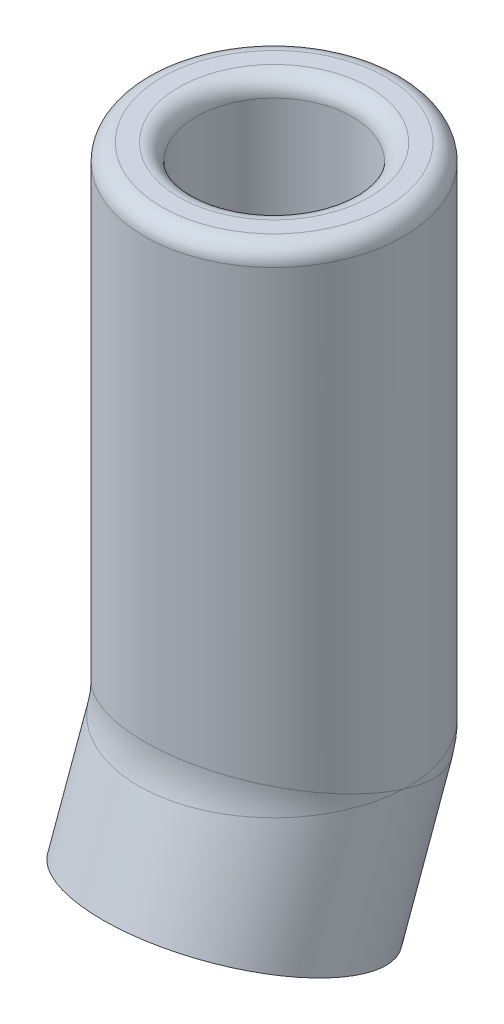
SolidWorks part; units mm, degrees
ref_plane "Front Plane" through (0, 0, 0) normal (0, 0, 1) x (1, 0, 0)
ref_plane "Top Plane" through (0, 0, 0) normal (0, 1, 0) x (1, 0, 0)
ref_plane "Right Plane" through (0, 0, 0) normal (1, 0, 0) x (0, 0, -1)
sketch "Sketch1" plane through (0, 0, 0) normal (0, 1, 0) x (1, 0, 0)
  circle A0 centre (0, 0) radius 4.575
  circle A1 centre (0, 0) radius 7.575
  dimension "D1" = 9.15
  dimension "D2" = 3
extrude "Boss-Extrude1" add sketch "Sketch1" along normal blind 25
sketch "Sketch2" plane through (0, 0, 0) normal (0, 1, 0) x (1, 0, 0)
  circle A0 centre (0, 0) radius 7.575 construction
  circle A1 centre (0, 0) radius 7.575
sketch "Sketch3" plane through (0, 0, 0) normal (1, 0, 0) x (0, 0, -1)
  line L0 (0, 0) -> (0, -4)
  line L1 (0, -4) -> (-2.9118, -12)
  dimension "D1" = 4
  dimension "D2" = 8
  dimension "D3" = 160
sweep "Sweep1" add profiles "Sketch2" path "Sketch3"
fillet "Fillet2" radius 6 1 edges at (0, -5.3357, -7.575)
fillet "Fillet3" radius 1 1 edges at (0, 25, 7.575)
fillet "Fillet4" radius 1 1 edges at (0, 25, 4.575)
